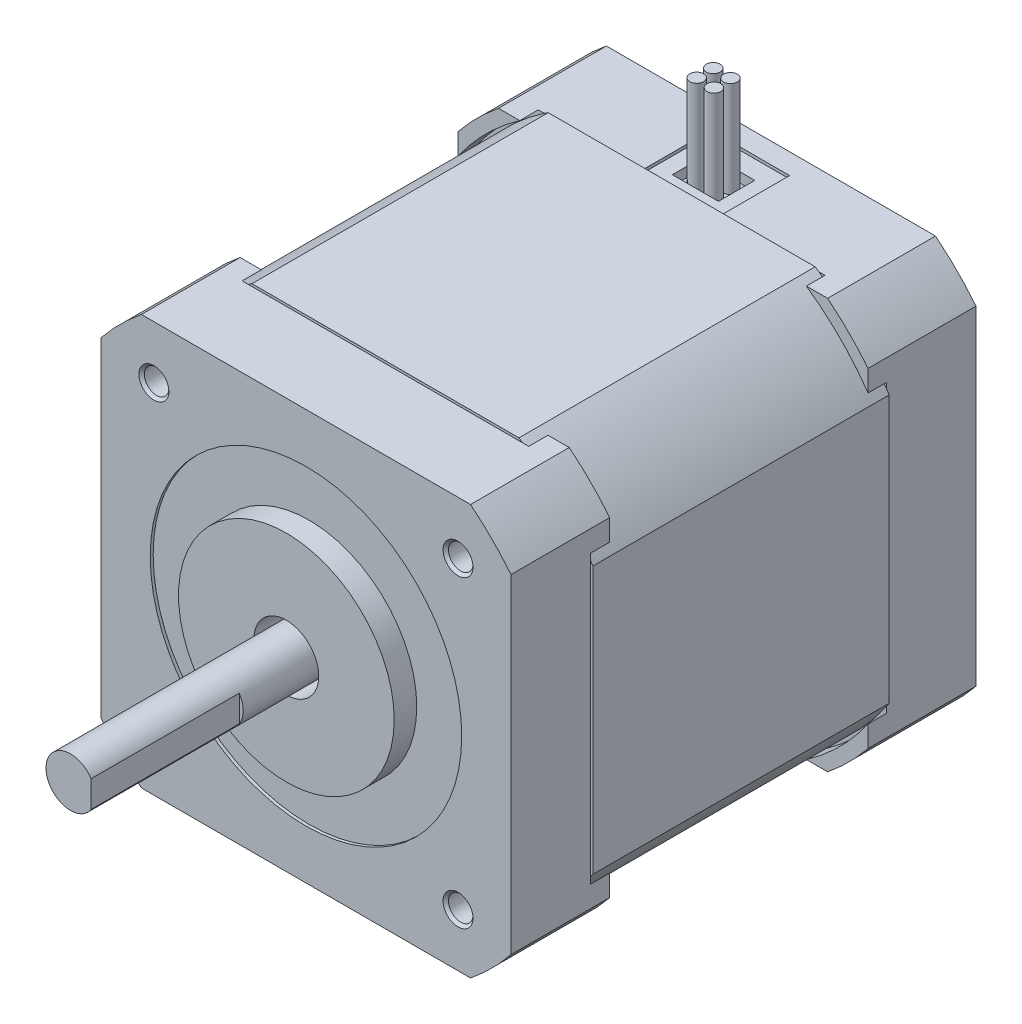
SolidWorks part; units mm, degrees
ref_plane "Спереди" through (0, 0, 0) normal (0, 0, 1) x (1, 0, 0)
ref_plane "Сверху" through (0, 0, 0) normal (0, 1, 0) x (1, 0, 0)
ref_plane "Справа" through (0, 0, 0) normal (1, 0, 0) x (0, 0, -1)
sketch "Эскиз1" plane through (0, 0, 0) normal (0, 0, 1) x (1, 0, 0)
  line L1 (20.9, 20.9) -> (-20.9, 20.9)
  line L2 (20.9, 20.9) -> (20.9, -20.9)
  line L3 (20.9, -20.9) -> (-20.9, -20.9)
  line L4 (-20.9, 20.9) -> (-20.9, -20.9)
  line L5 (0, -20.9) -> (0, 20.9) construction
  line L6 (20.9, 0) -> (-20.9, 0) construction
  circle A0 centre (0, 0) radius 26.8
  point P0 (0, 0)
  dimension "D2" = 53.6
  dimension "D1" = 41.8
extrude "Бобышка-Вытянуть1" add sketch "Эскиз1" along normal blind 11 contours L2 A0 L1 L4 L3 region at (0, 0, 0)
sketch "Эскиз2" plane through (0, 0, 11) normal (0, 0, 1) x (1, 0, 0)
  circle A0 centre (0, 0) radius 25.5
  dimension "D1" = 51
extrude "Вырез-Вытянуть1" cut sketch "Эскиз2" against normal blind 1.9
sketch "Эскиз3" plane through (0, 0, 9.1) normal (0, 0, 1) x (1, 0, 0)
  line L1 (21.15, 21.15) -> (-21.15, 21.15)
  line L2 (21.15, 21.15) -> (21.15, -21.15)
  line L3 (21.15, -21.15) -> (-21.15, -21.15)
  line L4 (-21.15, 21.15) -> (-21.15, -21.15)
  line L5 (0, -21.15) -> (0, 21.15) construction
  line L6 (21.15, 0) -> (-21.15, 0) construction
  circle A0 centre (0, 0) radius 25.15
  line M2 (14.6096, 20.9) -> (-14.6096, 20.9)
  line M4 (-20.9, 14.6096) -> (-20.9, -14.6096)
  line M6 (-14.6096, -20.9) -> (14.6096, -20.9)
  line M8 (20.9, -14.6096) -> (20.9, 14.6096)
  dimension "D1" = 50.3
  dimension "D2" = 42.3
extrude "Бобышка-Вытянуть2" add sketch "Эскиз3" along normal blind 30.2 contours A0 M8 M2 M4 M6 | A0 L1 M2 | L2 A0 M8 | A0 L3 M6 | A0 L4 M4 region at (0, 21.0244, 9.1) region at (21.0244, 0, 9.1) region at (0, 0, 9.1) region at (-21.0244, 0, 9.1) region at (0, -21.0244, 9.1)
extrude "Бобышка-Вытянуть3" add sketch "Эскиз1<3>" along normal offset from surface (8.1 mm away) 47.4 from surface contours L2 A0 L1 L4 L3 region at (0, 0, 0) up to face at (0, 0, 0) starting at face at (0, 0, 39.3)
sketch "Эскиз1<3>" plane through (0, 0, 0) normal (0, 0, 1) x (1, 0, 0) same geometry as "Эскиз1"
sketch "Эскиз4" plane through (0, 0, 39.3) normal (0, 0, -1) x (-1, 0, 0)
  line L0 (14.6096, 20.9) -> (16.7759, 20.9) construction
  line L1 (20.9, 16.7759) -> (20.9, 14.6096) construction
  line L2 (20.9, -14.6096) -> (20.9, -16.7759) construction
  line L3 (16.7759, -20.9) -> (14.6096, -20.9) construction
  line L4 (-14.6096, -20.9) -> (-16.7759, -20.9) construction
  line L5 (-20.9, -16.7759) -> (-20.9, -14.6096) construction
  line L6 (-20.9, 14.6096) -> (-20.9, 16.7759) construction
  line L7 (-16.7759, 20.9) -> (-14.6096, 20.9) construction
  line L8 (14.6096, 20.9) -> (16.7759, 20.9)
  line L9 (20.9, 16.7759) -> (20.9, 14.6096)
  line L10 (20.9, -14.6096) -> (20.9, -16.7759)
  line L11 (16.7759, -20.9) -> (14.6096, -20.9)
  line L12 (-14.6096, -20.9) -> (-16.7759, -20.9)
  line L13 (-20.9, -16.7759) -> (-20.9, -14.6096)
  line L14 (-20.9, 14.6096) -> (-20.9, 16.7759)
  line L15 (-16.7759, 20.9) -> (-14.6096, 20.9)
  arc A0 (20.9, 14.6096) -> (14.6096, 20.9) centre (0, 0) ccw construction
  arc A1 (20.9, 16.7759) -> (16.7759, 20.9) centre (0, 0) ccw construction
  arc A2 (14.6096, -20.9) -> (20.9, -14.6096) centre (0, 0) ccw construction
  arc A3 (16.7759, -20.9) -> (20.9, -16.7759) centre (0, 0) ccw construction
  arc A4 (-20.9, -14.6096) -> (-14.6096, -20.9) centre (0, 0) ccw construction
  arc A5 (-20.9, -16.7759) -> (-16.7759, -20.9) centre (0, 0) ccw construction
  arc A6 (-14.6096, 20.9) -> (-20.9, 14.6096) centre (0, 0) ccw construction
  arc A7 (-16.7759, 20.9) -> (-20.9, 16.7759) centre (0, 0) ccw construction
  arc A8 (20.9, 14.6096) -> (14.6096, 20.9) centre (0, 0) ccw
  arc A9 (20.9, 16.7759) -> (16.7759, 20.9) centre (0, 0) ccw
  arc A10 (14.6096, -20.9) -> (20.9, -14.6096) centre (0, 0) ccw
  arc A11 (16.7759, -20.9) -> (20.9, -16.7759) centre (0, 0) ccw
  arc A12 (-20.9, -14.6096) -> (-14.6096, -20.9) centre (0, 0) ccw
  arc A13 (-20.9, -16.7759) -> (-16.7759, -20.9) centre (0, 0) ccw
  arc A14 (-14.6096, 20.9) -> (-20.9, 14.6096) centre (0, 0) ccw
  arc A15 (-16.7759, 20.9) -> (-20.9, 16.7759) centre (0, 0) ccw
extrude "Бобышка-Вытянуть4" add sketch "Эскиз4" along normal blind 1.96
sketch "Эскиз5" plane through (0, 0, 47.4) normal (0, 0, 1) x (1, 0, 0)
  circle A0 centre (0, 0) radius 15.875
  dimension "D1" = 31.75
extrude "Вырез-Вытянуть2" cut sketch "Эскиз5" against normal blind 0.3
sketch "Эскиз6" plane through (0, 0, 47.1) normal (0, 0, 1) x (1, 0, 0)
  circle A0 centre (0, 0) radius 10.995
  dimension "D1" = 21.99
extrude "Бобышка-Вытянуть5" add sketch "Эскиз6" along normal blind 2.3
sketch "Эскиз7" plane through (0, 0, 49.4) normal (0, 0, 1) x (1, 0, 0)
  circle A0 centre (0, 0) radius 3.3
  dimension "D1" = 6.6
extrude "Вырез-Вытянуть3" cut sketch "Эскиз7" against normal blind 5
sketch "Эскиз8" plane through (0, 0, 44.4) normal (0, 0, 1) x (1, 0, 0)
  circle A0 centre (0, 0) radius 2.5
  dimension "D1" = 5
extrude "Бобышка-Вытянуть7" add sketch "Эскиз8" along normal offset from surface (27 mm away) 22 up to face at (3.3, 0, 49.4) offset beyond the face yes
sketch "Эскиз9" plane through (0, 0, 71.4) normal (0, 0, 1) x (1, 0, 0)
  line L1 (2.1, 1.3565) -> (2.5, 1.3565)
  line L2 (2.1, 1.3565) -> (2.1, -1.3565)
  line L3 (2.1, -1.3565) -> (2.5, -1.3565)
  line L4 (2.5, 1.3565) -> (2.5, -1.3565)
  circle A0 centre (0, 0) radius 2.5 construction
  dimension "D1" = 4.6
extrude "Вырез-Вытянуть4" cut sketch "Эскиз9" against normal blind 15.1
hole_wizard "Отверстие обработанное метчиком M31" positions "Эскиз10" profile "Эскиз11" tap size "M3" standard "DIN"
sketch "Эскиз10" plane through (0, 0, 47.4) normal (0, 0, 1) x (1, 0, 0)
  point P0 (-15.5, 15.5)
  dimension "D1" = 15.5
  dimension "D2" = 15.5
sketch "Эскиз11" plane through (-15.5, 15.5, 47.4) normal (1, 0, 0) x (0, -1, 0)
  line L0 (0, 0) -> (0, 6.7511)
  line L1 (0, 6.7511) -> (1.25, 6)
  line L2 (1.25, 6) -> (1.25, 0.275)
  line L3 (1.25, 0.275) -> (1.525, 0)
  line L5 (1.525, 0) -> (0, 0)
  line L6 (-1.25, 0.275) -> (-1.525, 0) construction
  line L10 (0, 6.7511) -> (-1.25, 6) construction
  line L11 (0, -6.35) -> (0, 107.95) construction
  dimension "Диаметр сверла" = 2.5
  dimension "Глубина сверла" = 6
  dimension "Диаметр передней зенковки" = 3.05
  dimension "Угол передней зенковки" = 90
  dimension "Угол заточки сверла" = 118
cosmetic thread "Отверстие резьбы1" parameters "D1"=4.5, "D2"=3
sketch "Эскиз12" plane through (0, 0, 0) normal (0, 0, -1) x (-1, 0, 0)
  circle A0 centre (15.5, 15.5) radius 3
  dimension "D1" = 6
extrude "Вырез-Вытянуть5" cut sketch "Эскиз12" against normal blind 0.3
sketch "Эскиз13" plane through (0, 0, 0.3) normal (0, 0, -1) x (-1, 0, 0)
  line L1 (15.0809, 17.4616) -> (15.9191, 17.4616)
  line L2 (15.0809, 17.4616) -> (15.0809, 13.5384)
  line L3 (15.0809, 13.5384) -> (15.9191, 13.5384)
  line L4 (15.9191, 17.4616) -> (15.9191, 13.5384)
  line L5 (15.5, 13.5384) -> (15.5, 17.4616) construction
  line L6 (15.0809, 15.5) -> (15.9191, 15.5) construction
  line L7 (13.5384, 15.9191) -> (17.4616, 15.9191)
  line L8 (13.5384, 15.9191) -> (13.5384, 15.0809)
  line L9 (13.5384, 15.0809) -> (17.4616, 15.0809)
  line L10 (17.4616, 15.9191) -> (17.4616, 15.0809)
  line L11 (15.5, 15.0809) -> (15.5, 15.9191) construction
  line L12 (13.5384, 15.5) -> (17.4616, 15.5) construction
  point P0 (15.5, 15.5)
  point P4 (15.5, 15.5)
extrude "Вырез-Вытянуть6" cut sketch "Эскиз13" against normal blind 2 contours L8 L9 L2 L7 | L2 L7 L4 L1 | L2 L9 L4 L7 | L10 L7 L4 L9 | L9 L2 L3 L4 region at (-15.5, 16.6903, 0.3) region at (-15.5, 15.5, 0.3) region at (-14.3097, 15.5, 0.3) region at (-16.6903, 15.5, 0.3) region at (-15.5, 14.3097, 0.3)
chamfer "Фаска1" distance 1.54 angle 45 4 edges at (-13.5384, 15.5, 2.3) (-15.5, 13.5384, 2.3) (-17.4616, 15.5, 2.3) (-15.5, 17.4616, 2.3)
fillet "Скругление1" radius 0.5 4 edges at (-15.0809, 15.0809, 1.3) (-15.9191, 15.0809, 1.3) (-15.0809, 15.9191, 1.3) (-15.9191, 15.9191, 1.3)
pattern_circular "Круговой массив1" count 4 over 360 about axis through (0, 0, 100.4711) along (0, 0, -1) of "Отверстие обработанное метчиком M31", "Вырез-Вытянуть5", "Вырез-Вытянуть6", "Фаска1", "Скругление1" reverse direction yes
cosmetic thread "Отверстие резьбы2" parameters "D1"=4.5, "D2"=3
cosmetic thread "Отверстие резьбы3" parameters "D1"=4.5, "D2"=3
cosmetic thread "Отверстие резьбы4" parameters "D1"=4.5, "D2"=3
sketch "Эскиз14" plane through (0, 20.9, 0) normal (0, 1, 0) x (1, 0, 0)
  line L0 (13.9897, -9.1) -> (-13.9897, -9.1) construction
  line L1 (-4, -2.1) -> (4, -2.1)
  line L2 (-4, -2.1) -> (-4, -9.1)
  line L3 (-4, -9.1) -> (4, -9.1)
  line L4 (4, -2.1) -> (4, -9.1)
  point P4 (0, -9.1)
  dimension "D1" = 8
  dimension "D2" = 7
extrude "Вырез-Вытянуть7" cut sketch "Эскиз14" against normal blind 0.3
sketch "Эскиз15" plane through (0, 20.6, 0) normal (0, 1, 0) x (1, 0, 0)
  line L0 (16.7759, 0) -> (-16.7759, 0) construction
  line L1 (-2.35, -4) -> (2.35, -4)
  line L2 (-2.35, -4) -> (-2.35, -7.7)
  line L3 (-2.35, -7.7) -> (2.35, -7.7)
  line L4 (2.35, -4) -> (2.35, -7.7)
  point P4 (0, -7.7)
  dimension "D1" = 3.7
  dimension "D2" = 4.7
  dimension "D3" = 4
extrude "Вырез-Вытянуть8" cut sketch "Эскиз15" against normal blind 1
sketch "Эскиз16" plane through (0, 19.6, 0) normal (0, 1, 0) x (1, 0, 0)
  line L0 (0, -7.7) -> (0, -4) construction
  line L1 (-2.35, -7.7) -> (2.35, -7.7) construction
  line L2 (2.35, -4) -> (-2.35, -4) construction
  line L3 (2.35, -5.85) -> (-2.35, -5.85) construction
  line L4 (2.35, -7.7) -> (2.35, -4) construction
  line L5 (-2.35, -4) -> (-2.35, -7.7) construction
  circle A0 centre (-0.8763, -6.6921) radius 0.7
  circle A1 centre (0.8763, -6.6921) radius 0.7
  circle A2 centre (0.8763, -5.0079) radius 0.7
  circle A3 centre (-0.8763, -5.0079) radius 0.7
  dimension "D1" = 1.4
extrude "Бобышка-Вытянуть8" add sketch "Эскиз16" along normal blind 9.8
